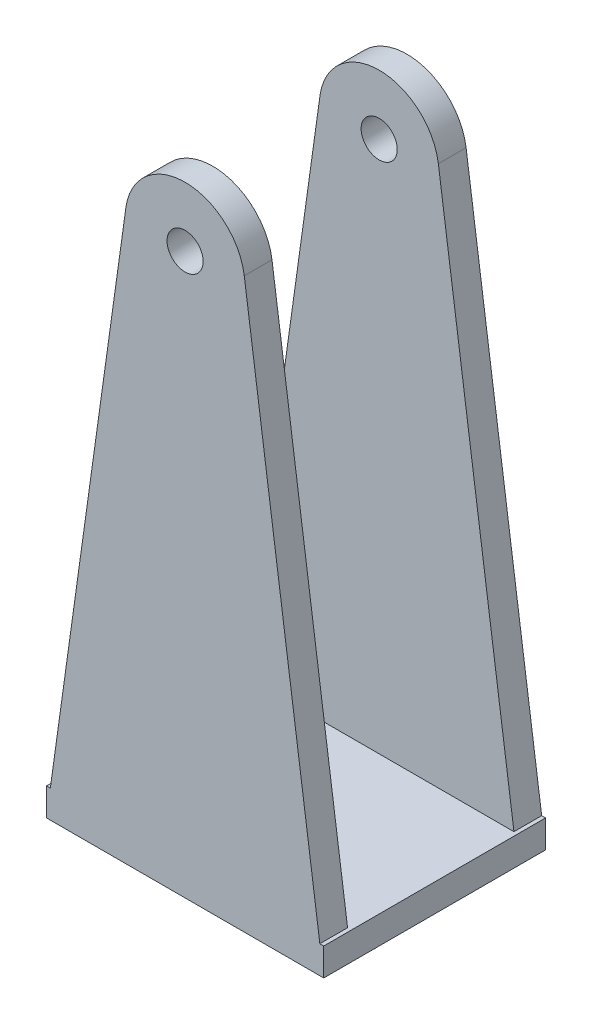
SolidWorks part; units mm, degrees
material "PBT General Purpose"
ref_plane "Front Plane" through (0, 0, 0) normal (0, 0, 1) x (1, 0, 0)
ref_plane "Top Plane" through (0, 0, 0) normal (0, 1, 0) x (1, 0, 0)
ref_plane "Right Plane" through (0, 0, 0) normal (1, 0, 0) x (0, 0, -1)
sketch "Sketch1" plane through (0, 0, 0) normal (0, 1, 0) x (1, 0, 0)
  line L1 (-12.5, -10) -> (12.5, -10)
  line L2 (-12.5, -10) -> (-12.5, 10)
  line L3 (-12.5, 10) -> (12.5, 10)
  line L4 (12.5, -10) -> (12.5, 10)
  line L5 (-12.5, -10) -> (12.5, 10) construction
  line L6 (-12.5, 10) -> (12.5, -10) construction
  point P0 (0, 0)
  dimension "D1" = 20
  dimension "D2" = 25
extrude "Boss-Extrude1" add sketch "Sketch1" along normal blind 2.5
ref_plane "Plane1" through (0, 0, 0) normal (0, 0, -1) x (-1, 0, 0)
sketch "Sketch4" plane through (0, 0, 0) normal (0, -1, 0) x (1, 0, 0)
  line L0 (12.5, -10) -> (-12.5, -10) construction
  circle A0 centre (0, 0) radius 10
extrude "Boss-Extrude3" add sketch "Sketch4" along normal blind 1
sketch "Sketch6" plane through (0, 0, -10) normal (0, 0, -1) x (-1, 0, 0)
  line L1 (12.5, 0) -> (-12.5, 0)
  line L2 (12.5, 0) -> (5.3349, 51.2454)
  line L5 (-10, -1) -> (10, -1) construction
  line L6 (-10, -1) -> (10, -1)
  line L7 (0, -1) -> (0, 50.5) construction
  line L8 (-12.5, 0) -> (-5.3349, 51.2454)
  line L9 (0, 52.127) -> (0, 55.8867) construction
  circle A0 centre (0, 50.5) radius 1.627
  arc A1 (5.3349, 51.2454) -> (-5.3349, 51.2454) centre (0, 50.5) ccw
  line M10 (12.5, 2.5) -> (-12.5, 2.5)
  dimension "D2" = 3.254
  dimension "D3" = 3.7597
extrude "Boss-Extrude5" add sketch "Sketch6" against normal blind 2.5 contours L2 A1 L8 A0 M10 region at (0, 24.7101, -10)
sketch "Sketch5" plane through (0, -1, 0) normal (0, -1, 0) x (1, 0, 0)
  circle A0 centre (0, 0) radius 4.9365
  dimension "D1" = 9.873
mirror "Mirror2" about plane through (0, 0, 0) normal (0, 0, -1) of "Boss-Extrude5"
sketch "Sketch7" plane through (0, -1, 0) normal (0, -1, 0) x (1, 0, 0)
  line L1 (-12.5, 10) -> (12.5, 10)
  line L2 (-12.5, 10) -> (-12.5, -10)
  line L3 (-12.5, -10) -> (12.5, -10)
  line L4 (12.5, 10) -> (12.5, -10)
extrude "Cut-Extrude2" cut sketch "Sketch7" against normal up to vertex (1 mm away) contours L2 L3 L4 L1 up to point (-12.5, 0, 10)
sketch "Sketch8" plane through (0, 0, 0) normal (0, -1, 0) x (1, 0, 0)
  line L0 (-12.5, 10) -> (12.5, 10) construction
  line L1 (10, -10) -> (-10, -10) construction
  line L2 (10, -10) -> (10, 10) construction
  line L3 (10, 10) -> (-10, 10) construction
  line L4 (-10, -10) -> (-10, 10) construction
  line L5 (10, -10) -> (-10, 10) construction
  line L6 (10, 10) -> (-10, -10) construction
  circle A0 centre (-4.9497, -4.9497) radius 1
  circle A1 centre (4.9497, 4.9497) radius 1
  point P0 (0, 0)
  dimension "D1" = 2
  dimension "D2" = 14
extrude "Cut-Extrude3" cut sketch "Sketch8" against normal through all
